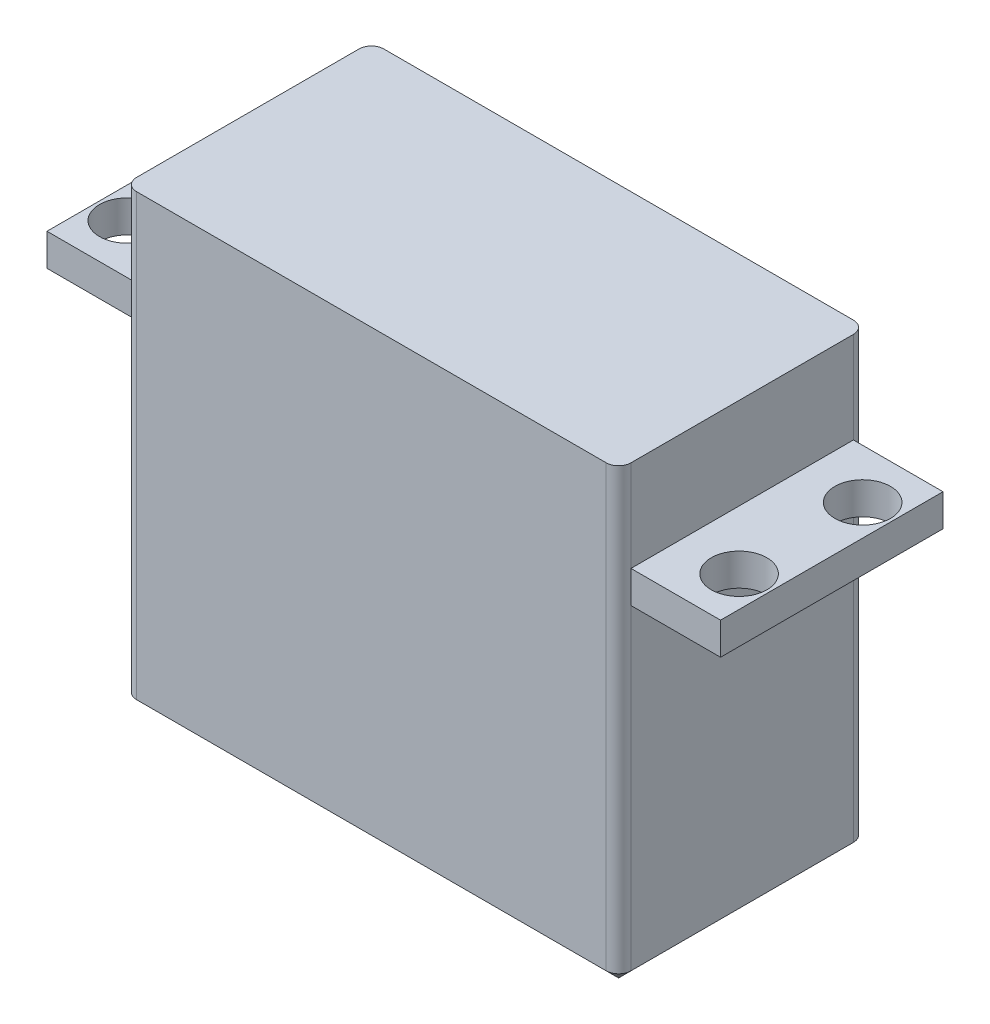
SolidWorks part; units mm, degrees
ref_plane "Front Plane" through (0, 0, 0) normal (0, 0, 1) x (1, 0, 0)
ref_plane "Top Plane" through (0, 0, 0) normal (0, 1, 0) x (1, 0, 0)
ref_plane "Right Plane" through (0, 0, 0) normal (1, 0, 0) x (0, 0, -1)
sketch "Sketch1" plane through (0, 0, 0) normal (0, 1, 0) x (1, 0, 0)
  line L1 (-20, 10) -> (20, 10)
  line L2 (-20, 10) -> (-20, -10)
  line L3 (-20, -10) -> (20, -10)
  line L4 (20, 10) -> (20, -10)
  line L5 (-20, 10) -> (20, -10) construction
  line L6 (-20, -10) -> (20, 10) construction
  point P0 (0, 0)
  dimension "D1" = 20
  dimension "D2" = 40
extrude "Boss-Extrude1" add sketch "Sketch1" along normal blind 36.6
sketch "Sketch2" plane through (20, 0, 0) normal (1, 0, 0) x (0, 0, -1)
  line L0 (-10, 0) -> (10, 0) construction
  line L1 (-9, 29.2) -> (9, 29.2)
  line L2 (-9, 29.2) -> (-9, 26.6)
  line L3 (-9, 26.6) -> (9, 26.6)
  line L4 (9, 29.2) -> (9, 26.6)
  dimension "D1" = 26.6
  dimension "D2" = 2.6
  dimension "D3" = 18
  dimension "D4" = 9
extrude "Boss-Extrude2" add sketch "Sketch2" along normal blind 7.25
sketch "Sketch3" plane through (0, 29.2, 0) normal (0, 1, 0) x (1, 0, 0)
  circle A0 centre (24.75, 5) radius 2.25
  dimension "D2" = 4.5
  dimension "D1" = 5
  dimension "D3" = 24.75
extrude "Cut-Extrude1" cut sketch "Sketch3" against normal through all
mirror "Mirror2" about plane through (0, 0, 0) normal (0, 0, 1) of "Cut-Extrude1"
mirror "Mirror3" about plane through (0, 0, 0) normal (1, 0, 0) of "Boss-Extrude2", "Cut-Extrude1", "Mirror2"
sketch "Sketch4" plane through (0, 36.6, 0) normal (0, 1, 0) x (1, 0, 0)
  line L0 (20, 9) -> (20, -9) construction
  circle A0 centre (9.9, 0) radius 4
  dimension "D1" = 8
  dimension "D2" = 10.1
fillet "Fillet1" radius 1 4 edges at (20, 18.3, 10) (20, 18.3, -10) (-20, 18.3, -10) (-20, 18.3, 10)
chamfer "Chamfer1" distance 1 angle 45 8 edges at (20, 0, 0) (0, 0, 10) (-20, 0, 0) (19.7071, 0, 9.7071) (-19.7071, 0, 9.7071) (19.7071, 0, -9.7071) (-19.7071, 0, -9.7071) (0, 0, -10)
ref_axis "Axis1" through (9.9, 36.6, 0) along (0, 1, 0)
